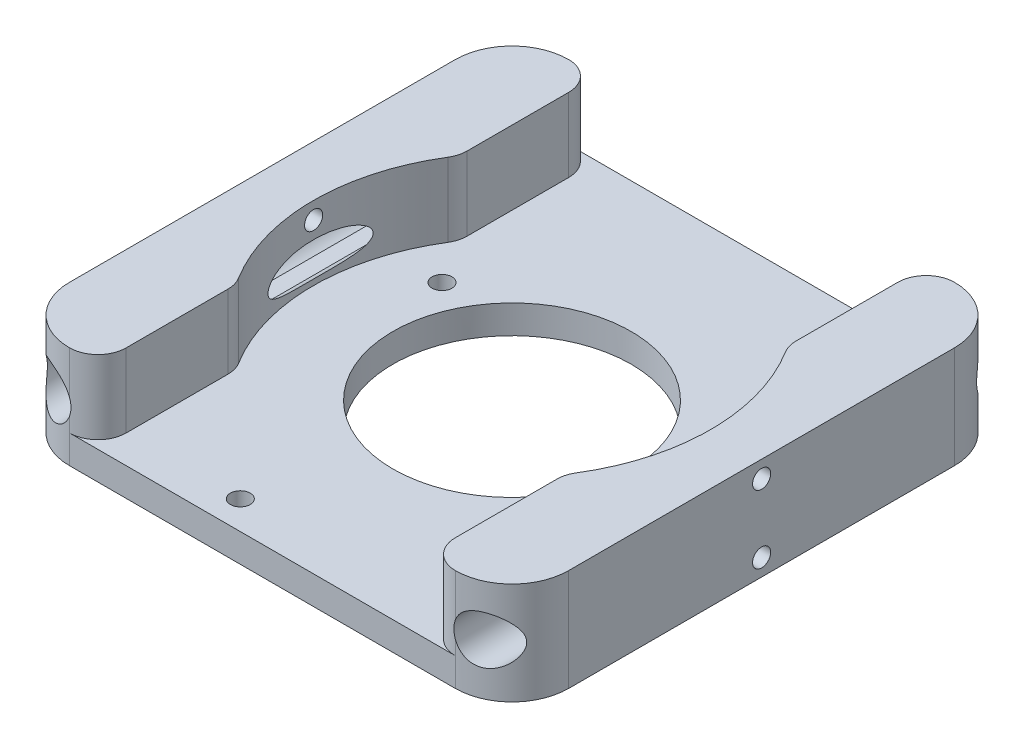
SolidWorks part; units mm, degrees
ref_plane "Front Plane" through (0, 0, 0) normal (0, 0, 1) x (1, 0, 0)
ref_plane "Top Plane" through (0, 0, 0) normal (0, 1, 0) x (1, 0, 0)
ref_plane "Right Plane" through (0, 0, 0) normal (1, 0, 0) x (0, 0, -1)
sketch "Sketch1" plane through (0, 0, 0) normal (0, 1, 0) x (1, 0, 0)
  line L0 (-44, 0) -> (-44, -44) construction
  line L1 (-44, -44) -> (44, -44) construction
  line L2 (44, -44) -> (44, 0) construction
  line L4 (-44, -44) -> (44, -44)
  line L5 (-44, -44) -> (-44, 44)
  line L6 (-44, 44) -> (44, 44)
  line L7 (44, -44) -> (44, 44)
  arc A0 (44, 0) -> (-44, 0) centre (0, 0) ccw construction
  dimension "D1" = 88
extrude "Boss-Extrude1" add sketch "Sketch1" along normal blind 18
sketch "Sketch2" plane through (0, 0, 44) normal (0, 0, 1) x (1, 0, 0)
  line L1 (-1044, 9) -> (48956, 9) construction
  line L2 (0, -1000) -> (0, 49000) construction
  line L3 (-44, 18) -> (-44, 0) construction
  circle A0 centre (-38, 9) radius 4.25
  circle A1 centre (38, 9) radius 4.25
  point P7 (-44, 9)
  dimension "D1" = 8.5
  dimension "D2" = 6
extrude "Cut-Extrude1" cut sketch "Sketch2" against normal through all
fillet "Fillet1" radius 10 4 edges at (44, 9, 44) (-44, 9, 44) (44, 9, -44) (-44, 9, -44)
sketch "Sketch3" plane through (0, 18, 0) normal (0, 1, 0) x (1, 0, 0)
  circle A0 centre (0, 0) radius 35
  dimension "D1" = 70
extrude "Cut-Extrude2" cut sketch "Sketch3" against normal through all
sketch "Sketch5" plane through (0, 0, 0) normal (0, 1, 0) x (1, 0, 0)
  line L0 (-44, 34) -> (-44, -34) construction
  circle A0 centre (0, 0) radius 44
  circle A1 centre (0, 0) radius 35
  circle A3 centre (0, 0) radius 35 construction
extrude "Boss-Extrude2" add sketch "Sketch5" along normal blind 5
sketch "Sketch8" plane through (0, 18, 0) normal (0, 1, 0) x (1, 0, 0)
  line L0 (-34, -44) -> (34, -44) construction
  line L1 (29, 46) -> (-29, 46)
  line L2 (29, 46) -> (29, -46)
  line L3 (29, -46) -> (-29, -46)
  line L4 (-29, 46) -> (-29, -46)
  line L5 (29, 46) -> (-29, -46) construction
  line L6 (29, -46) -> (-29, 46) construction
  point P0 (0, 0)
  dimension "D1" = 58
  dimension "D2" = 2
extrude "Cut-Extrude4" cut sketch "Sketch8" against normal up to surface (13 mm away) up to face at (-38.0405, 5, 0)
fillet "Fillet2" radius 5 8 edges at (29, 11.5, 44) (29, 11.5, 19.5959) (29, 11.5, -44) (29, 11.5, -19.5959) (-29, 11.5, -44) (-29, 11.5, -19.5959) (-29, 11.5, 19.5959) (-29, 11.5, 44)
sketch "Sketch12" plane through (44, 0, 0) normal (1, 0, 0) x (0, 0, -1)
  line L0 (-34, 0) -> (34, 0) construction
  line L1 (-34, 18) -> (34, 18) construction
  circle A0 centre (0, 15) radius 1.6
  circle A1 centre (0, 3) radius 1.6
  dimension "D1" = 3.2
  dimension "D2" = 3
  dimension "D3" = 3
extrude "Cut-Extrude6" cut sketch "Sketch12" against normal up to next
mirror "Mirror1" about plane through (0, 0, 0) normal (1, 0, 0) of "Cut-Extrude6"
sketch "Sketch13" plane through (0, 5, 0) normal (0, 1, 0) x (1, 0, 0)
  line L1 (35, -41.5) -> (-35, -41.5) construction
  line L2 (35, -41.5) -> (35, 41.5) construction
  line L3 (35, 41.5) -> (-35, 41.5) construction
  line L4 (-35, -41.5) -> (-35, 41.5) construction
  line L5 (35, -41.5) -> (-35, 41.5) construction
  line L6 (35, 41.5) -> (-35, -41.5) construction
  circle A0 centre (24.13, 13.07) radius 1.75 construction
  circle A1 centre (-24.13, 11.8) radius 1.75 construction
  circle A2 centre (-8.89, -39) radius 1.75 construction
  point P0 (0, 0)
  dimension "D4" = 10.87
  dimension "D5" = 26.11
  dimension "D6" = 2.5
  dimension "D7" = 53.3
  dimension "D8" = 54.57
  dimension "D9" = 3.5
  dimension "D3" = 59.13
  dimension "D1" = 83
  dimension "D2" = 70
sketch "Sketch15" plane through (0, 5, 0) normal (0, 1, 0) x (1, 0, 0)
  line L0 (35, 41.5) -> (-35, -41.5) construction
  circle A0 centre (0, 0) radius 35
  arc A1 (29.75, 18.4374) -> (-29.75, 18.4374) centre (0, 0) ccw construction
  circle A2 centre (24.13, 13.07) radius 1.75
  circle A3 centre (-24.13, 11.8) radius 1.75
  circle A4 centre (24.13, 13.07) radius 1.75 construction
  circle A5 centre (-24.13, 11.8) radius 1.75 construction
extrude "Boss-Extrude3" add sketch "Sketch15" against normal up to surface (5 mm away) up to face at (0, 0, 0)
sketch "Sketch16" plane through (0, 5, 0) normal (0, 1, 0) x (1, 0, 0)
  circle A0 centre (-8.89, -39) radius 1.75
  circle A1 centre (-8.89, -39) radius 1.75 construction
extrude "Cut-Extrude7" cut sketch "Sketch16" against normal through all
sketch "Sketch17" plane through (0, 5, 0) normal (0, 1, 0) x (1, 0, 0)
  line L0 (35, -41.5) -> (-35, 41.5) construction
  circle A0 centre (0, 0) radius 21
  dimension "D1" = 42
extrude "Cut-Extrude8" cut sketch "Sketch17" against normal blind 10
